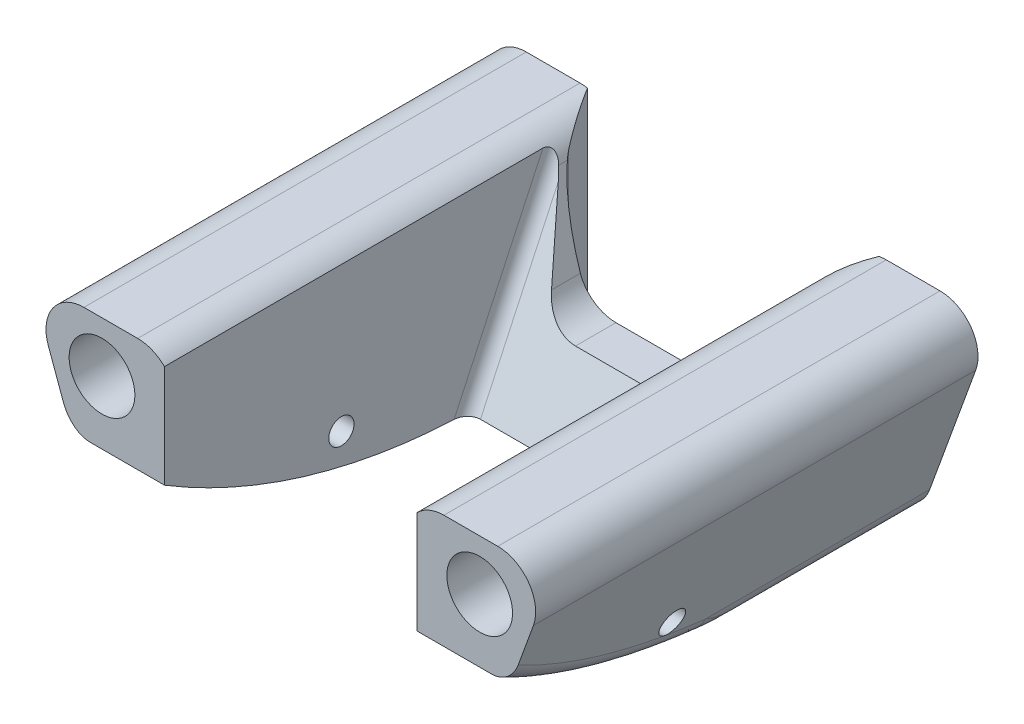
SolidWorks part; units mm, degrees
ref_plane "Front Plane" through (0, 0, 0) normal (0, 0, 1) x (1, 0, 0)
ref_plane "Top Plane" through (0, 0, 0) normal (0, 1, 0) x (1, 0, 0)
ref_plane "Right Plane" through (0, 0, 0) normal (1, 0, 0) x (0, 0, -1)
sketch "Sketch1" plane through (0, 0, 0) normal (0, 0, 1) x (1, 0, 0)
  line L0 (-19.1913, -37.0261) -> (-15.5516, -47.0261)
  line L1 (-12.7325, -49) -> (12.7325, -49)
  line L2 (15.5516, -47.0261) -> (19.1913, -37.0261)
  line L3 (-16.3722, -33) -> (-12.1155, -33)
  line L4 (-9.2964, -34.9739) -> (-7.0937, -41.0261)
  line L5 (-4.2746, -43) -> (4.2746, -43)
  line L6 (7.0937, -41.0261) -> (9.2964, -34.9739)
  line L7 (12.1155, -33) -> (16.3722, -33)
  circle A1 centre (-14.9441, -37) radius 2.6
  circle A3 centre (14.9441, -37) radius 2.6
  arc A4 (12.7325, -49) -> (15.5516, -47.0261) centre (12.7325, -46) ccw
  arc A5 (-15.5516, -47.0261) -> (-12.7325, -49) centre (-12.7325, -46) ccw
  arc A6 (19.1913, -37.0261) -> (16.3722, -33) centre (16.3722, -36) ccw
  arc A7 (-19.1913, -37.0261) -> (-16.3722, -33) centre (-16.3722, -36) cw
  arc A8 (-9.2964, -34.9739) -> (-12.1155, -33) centre (-12.1155, -36) ccw
  arc A9 (12.1155, -33) -> (9.2964, -34.9739) centre (12.1155, -36) ccw
  arc A10 (4.2746, -43) -> (7.0937, -41.0261) centre (4.2746, -40) ccw
  arc A11 (-7.0937, -41.0261) -> (-4.2746, -43) centre (-4.2746, -40) ccw
  dimension "D1" = 4
  dimension "D2" = 4
  dimension "D3" = 12
  dimension "D10" = 3
  dimension "D4" = 110
  dimension "D5" = 110
  dimension "D6" = 4
  dimension "D7" = 10
  dimension "D8" = 10
  dimension "D9" = 6
extrude "Boss-Extrude1" add sketch "Sketch1" along normal up to surface (35 mm away)
sketch "Sketch4" plane through (0, 0, 0) normal (1, 0, 0) x (0, 0, -1)
  line L0 (-35, -33) -> (0, -33) construction
  line L1 (-35, -49) -> (-11, -49)
  line L2 (-35, -49) -> (-35, -33)
  line L3 (-35, -33) -> (-3.5391, -33)
  line L5 (-11, -49) -> (-3.5391, -33)
  point P7 (-3.829, -33)
extrude "Cut-Extrude3" cut sketch "Sketch4" against normal mid plane 20
sketch "Sketch5" plane through (10, 0, 0) normal (-1, 0, 0) x (0, 0, 1)
  circle A0 centre (21, -45.3) radius 1 construction
  circle A1 centre (21, -45.3) radius 1
extrude "Cut-Extrude4" cut sketch "Sketch5" against normal through all both and the other way through all
sketch "Sketch6" plane through (0, -49, 0) normal (0, -1, 0) x (1, 0, 0)
  line L0 (-12.7325, 0) -> (12.7325, 0) construction
  line L1 (-11.5325, 0) -> (11.5325, 0)
  line L3 (-8.6458, 5) -> (8.6458, 5)
  line L7 (-11.5325, 0) -> (-8.6458, 5)
  line L8 (11.5325, 0) -> (8.6458, 5)
  dimension "D4" = 60
  dimension "D5" = 60
extrude "Cut-Extrude5" cut sketch "Sketch6" against normal through all
fillet "Fillet1" radius 3 2 edges at (-8.6458, -42.8808, 5) (8.6458, -42.8808, 5)
sketch "Sketch7" plane through (10, 0, 0) normal (-1, 0, 0) x (0, 0, 1)
  line L0 (38, -42) -> (35, -42) construction
  line L1 (38, -42) -> (35, -42) construction
  line L3 (35, -49) -> (0, -49) construction
  line L4 (10, -49) -> (0, -49) construction
  line L5 (35, -47.0261) -> (35, -37.0261) construction
  line L6 (35, -42) -> (35, -49)
  line L7 (35, -49) -> (10, -49)
  arc A0 (35, -42) -> (10, -49) centre (10, -0.8571) cw
  dimension "D1" = 25
extrude "Cut-Extrude6" cut sketch "Sketch7" against normal through all both and the other way through all
fillet "Fillet2" radius 1 2 edges at (-10, -41.4313, 7.4707) (10, -41.4313, 7.4707)
fillet "Fillet3" radius 2 4 edges at (-14.5903, -48.3556, 17.8508) (14.5903, -48.3556, 17.8508) (-16.3325, -44.8807, 29.4849) (16.3325, -44.8807, 29.4849)
